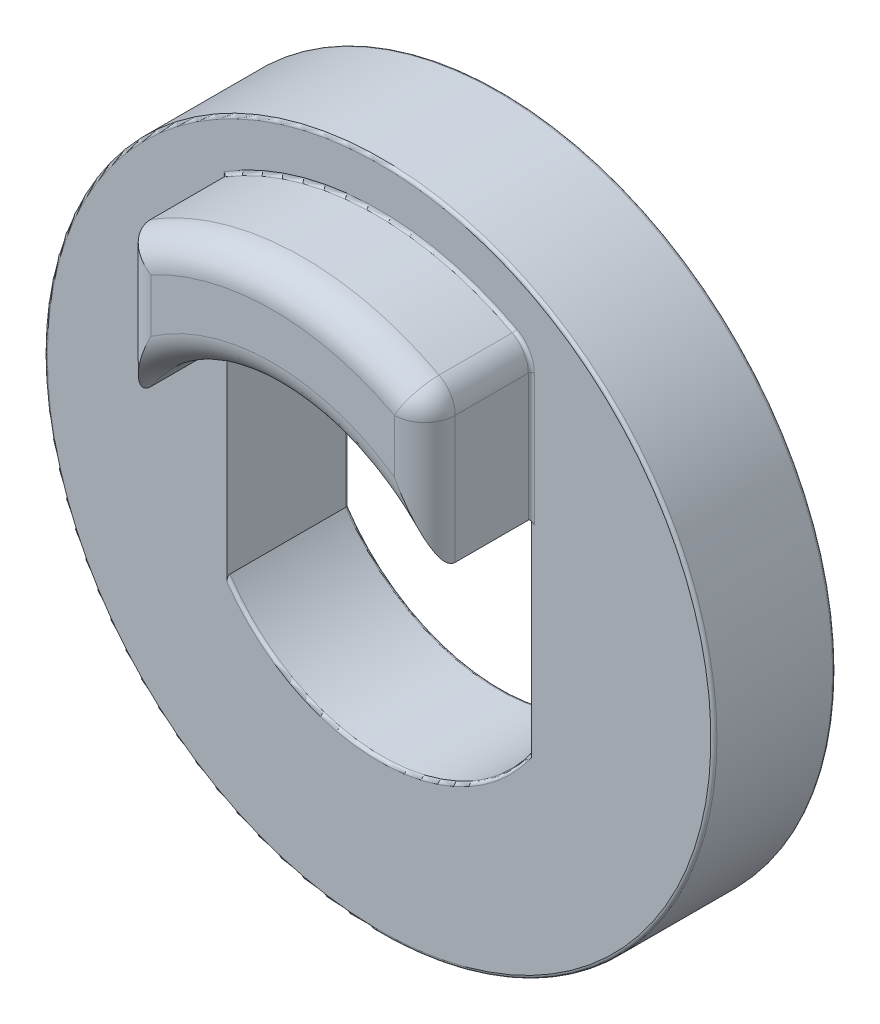
SolidWorks part; units mm, degrees
ref_plane "Alzado" through (0, 0, 0) normal (0, 0, 1) x (1, 0, 0)
ref_plane "Planta" through (0, 0, 0) normal (0, 1, 0) x (1, 0, 0)
ref_plane "Vista lateral" through (0, 0, 0) normal (1, 0, 0) x (0, 0, -1)
sketch "Croquis2" plane through (0, 0, 0) normal (1, 0, 0) x (0, 0, -1)
  line L0 (-7.5, 6) -> (0, 6)
  line L1 (-7.5, 0) -> (7.5, 0) construction
  line L2 (-7.5, 6) -> (-7.5, 9.5)
  line L3 (-7.5, 9.5) -> (-4, 9.5)
  line L4 (-4, 9.5) -> (-4, 11)
  line L5 (-4, 11) -> (0, 11)
  line L6 (0, 11) -> (0, 6)
  point P3 (-3.75, 6)
  point P7 (0, 0)
  dimension "D1" = 12
  dimension "D2" = 7.5
  dimension "D3" = 3.5
  dimension "D4" = 3.5
  dimension "D5" = 1.5
revolve "Revolución1" add sketch "Croquis2" angle 360 about L1
sketch "Croquis3" plane through (0, 0, 7.5) normal (0, 0, 1) x (1, 0, 0)
  line L1 (-5, 8.0777) -> (5, 8.0777)
  line L2 (-5, 8.0777) -> (-5, -8.0777)
  line L3 (-5, -8.0777) -> (5, -8.0777)
  line L4 (5, 8.0777) -> (5, -8.0777)
  line L5 (-5, 8.0777) -> (5, -8.0777) construction
  line L6 (-5, -8.0777) -> (5, 8.0777) construction
  circle A0 centre (0, 0) radius 9.5 construction
  circle A1 centre (0, 0) radius 6 construction
  circle A2 centre (0, 0) radius 9.5
  circle A3 centre (0, 0) radius 6
  circle M5 centre (0, 0) radius 6
  dimension "D1" = 10
extrude "Saliente-Extruir1" add sketch "Croquis3" against normal through all contours L4 M5 | L2 M5 region at (-5.403, 0, 7.5) region at (5.403, 0, 7.5)
sketch "Croquis4" plane through (0, 0, 7.5) normal (0, 0, 1) x (1, 0, 0)
  line L0 (5, 3.3166) -> (5, -3.3166) construction
  line L1 (-5, 8.0777) -> (5, 8.0777)
  line L2 (-5, 8.0777) -> (-5, -8.0777)
  line L3 (-5, -8.0777) -> (5, -8.0777)
  line L4 (5, 8.0777) -> (5, -8.0777)
  line L5 (-5, 8.0777) -> (5, -8.0777) construction
  line L6 (-5, -8.0777) -> (5, 8.0777) construction
  circle A0 centre (0, 0) radius 9.5 construction
  circle A1 centre (0, 0) radius 9.5
  point P9 (5, 0)
  point P10 (5, 0)
  line M3 (5, 3.3166) -> (5, -3.3166)
  arc M4 (5, -3.3166) -> (-5, -3.3166) centre (0, 0) cw
  line M5 (-5, -3.3166) -> (-5, 3.3166)
  circle M6 centre (0, 0) radius 9.5
extrude "Cortar-Extruir1" cut sketch "Croquis4" against normal up to surface (3.5 mm away) contours L4 M6 M3 | L2 M6 M5 | L4 L2 L3 M4 | L3 M6 region at (-6.8424, 0, 7.5) region at (6.8424, 0, 7.5) region at (0, -6.5407, 7.5) region at (0, -8.6505, 7.5) up to face at (9.5, 0, 4)
fillet "Redondeo1" radius 1 5 edges at (-5, 5.6972, 7.5) (0, 6, 7.5) (5, 5.6972, 7.5) (5, 8.0777, 5.75) (0, 9.5, 7.5)
fillet "Redondeo2" radius 0.1 11 edges at (-0.3054, 9.4951, 4) (4.8575, 8.0145, 4) (0, -6, 4) (-5, 5.6972, 4) (5, 5.4083, 4) (11, 0, 0) (11, 0, 4) (-5, 0, 0) (5, 0, 0) (0, 6, 0) (0, -6, 0)
